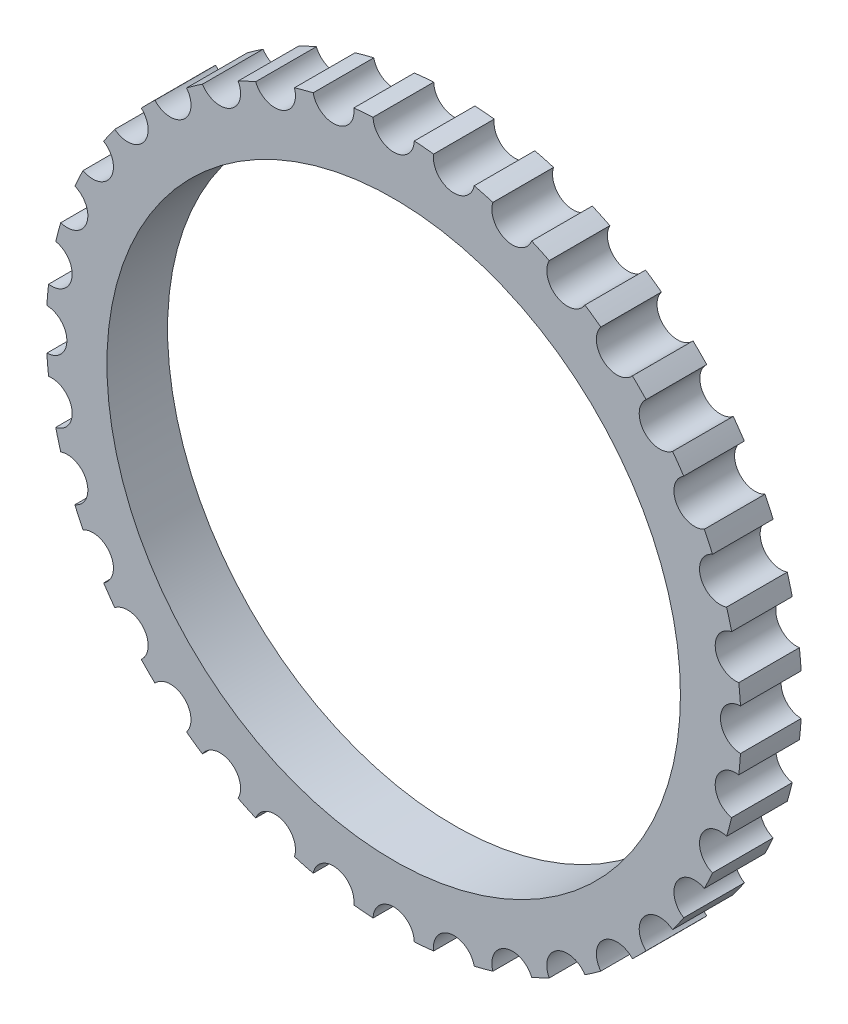
SolidWorks part; units mm, degrees
ref_plane "Front Plane" through (0, 0, 0) normal (0, 0, 1) x (1, 0, 0)
ref_plane "Top Plane" through (0, 0, 0) normal (0, 1, 0) x (1, 0, 0)
ref_plane "Right Plane" through (0, 0, 0) normal (1, 0, 0) x (0, 0, -1)
sketch "Sketch1" plane through (0, 0, 0) normal (0, 0, 1) x (1, 0, 0)
  circle A0 centre (0, 0) radius 23.6457
  circle A1 centre (0, 0) radius 28.6457
  dimension "D1" = 5
  dimension "D2" = 57.2914
extrude "Boss-Extrude1" add sketch "Sketch1" along normal blind 5
ref_plane "Plane1" through (0, 0, 2.5) normal (0, 0, 1) x (1, 0, 0)
sketch "Sketch2" plane through (0, 0, 2.5) normal (0, 0, 1) x (1, 0, 0)
  line L0 (15, 15) -> (-15, -15) construction
  line L1 (-15, -15) -> (15, -15) construction
  line L2 (-15, -15) -> (-15, 15) construction
  line L3 (-15, 15) -> (15, 15) construction
  line L4 (15, -15) -> (15, 15) construction
  circle A0 centre (-15, 15) radius 2.5
  circle A1 centre (15, 15) radius 2.5
  circle A2 centre (15, -15) radius 2.5
  circle A3 centre (-15, -15) radius 2.5
  point P4 (0, 0)
  dimension "D1" = 5
  dimension "D2" = 30
extrude "Boss-Extrude2" [suppressed] add sketch "Sketch2" along normal blind 15 and the other way blind 15
sketch "Sketch3" plane through (0, 0, 2.5) normal (0, 0, 1) x (1, 0, 0)
  circle A0 centre (0, 0) radius 28.6457 construction
  circle A1 centre (28.6457, 0) radius 1.7
  circle A2 centre (28.2105, -4.9743) radius 1.7
  circle A3 centre (26.9182, -9.7974) radius 1.7
  circle A4 centre (24.8079, -14.3229) radius 1.7
  circle A5 centre (21.9439, -18.4131) radius 1.7
  circle A6 centre (18.4131, -21.9439) radius 1.7
  circle A7 centre (14.3229, -24.8079) radius 1.7
  circle A8 centre (9.7974, -26.9182) radius 1.7
  circle A9 centre (4.9743, -28.2105) radius 1.7
  circle A10 centre (0, -28.6457) radius 1.7
  circle A11 centre (-4.9743, -28.2105) radius 1.7
  circle A12 centre (-9.7974, -26.9182) radius 1.7
  circle A13 centre (-14.3229, -24.8079) radius 1.7
  circle A14 centre (-18.4131, -21.9439) radius 1.7
  circle A15 centre (-21.9439, -18.4131) radius 1.7
  circle A16 centre (-24.8079, -14.3229) radius 1.7
  circle A17 centre (-26.9182, -9.7974) radius 1.7
  circle A18 centre (-28.2105, -4.9743) radius 1.7
  circle A19 centre (-28.6457, 0) radius 1.7
  circle A20 centre (-28.2105, 4.9743) radius 1.7
  circle A21 centre (-26.9182, 9.7974) radius 1.7
  circle A22 centre (-24.8079, 14.3229) radius 1.7
  circle A23 centre (-21.9439, 18.4131) radius 1.7
  circle A24 centre (-18.4131, 21.9439) radius 1.7
  circle A25 centre (-14.3229, 24.8079) radius 1.7
  circle A26 centre (-9.7974, 26.9182) radius 1.7
  circle A27 centre (-4.9743, 28.2105) radius 1.7
  circle A28 centre (0, 28.6457) radius 1.7
  circle A29 centre (4.9743, 28.2105) radius 1.7
  circle A30 centre (9.7974, 26.9182) radius 1.7
  circle A31 centre (14.3229, 24.8079) radius 1.7
  circle A32 centre (18.4131, 21.9439) radius 1.7
  circle A33 centre (21.9439, 18.4131) radius 1.7
  circle A34 centre (24.8079, 14.3229) radius 1.7
  circle A35 centre (26.9182, 9.7974) radius 1.7
  circle A36 centre (28.2105, 4.9743) radius 1.7
  point P75 (0, 0)
  dimension "D1" = 57.2914
  dimension "D2" = 3.4
  dimension "D3" = 36
extrude "Cut-Extrude1" cut sketch "Sketch3" against normal mid plane 16
